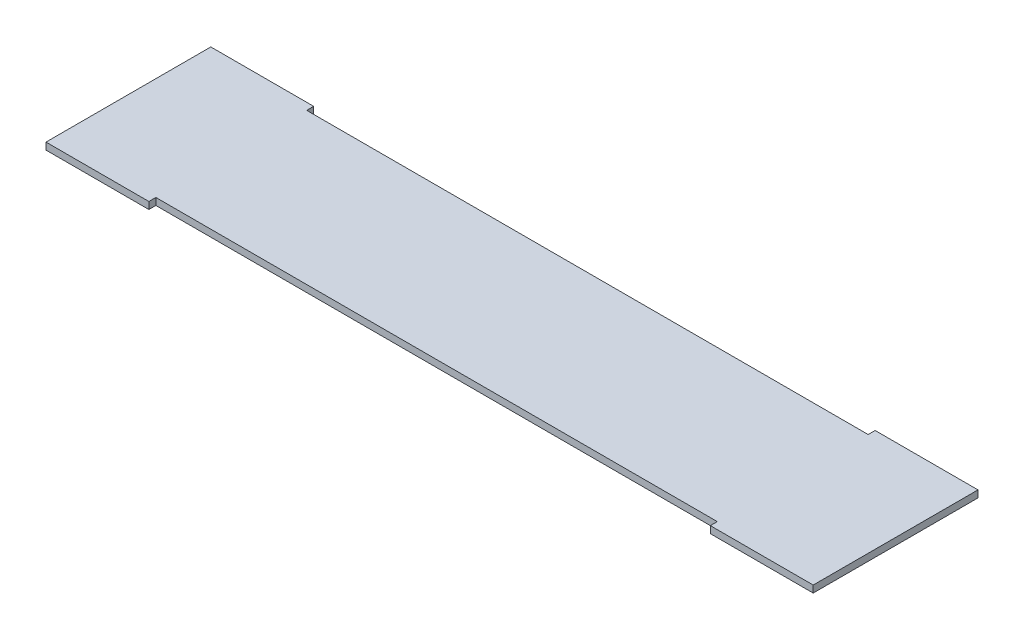
SolidWorks part; units mm, degrees
ref_plane "Front Plane" through (0, 0, 0) normal (0, 0, 1) x (1, 0, 0)
ref_plane "Top Plane" through (0, 0, 0) normal (0, 1, 0) x (1, 0, 0)
ref_plane "Right Plane" through (0, 0, 0) normal (1, 0, 0) x (0, 0, -1)
other "Default"
sketch "Sketch1" plane through (0, 0, 0) normal (0, 1, 0) x (1, 0, 0)
  line L0 (-349.15, 75) -> (-349.15, -75)
  line L1 (-349.15, -75) -> (-255.5, -75)
  line L2 (-255.5, -75) -> (-255.5, -68.65)
  line L3 (-255.5, -68.65) -> (255.5, -68.65)
  line L4 (255.5, -68.65) -> (255.5, -75)
  line L5 (255.5, -75) -> (349.15, -75)
  line L6 (349.15, -75) -> (349.15, 75)
  line L7 (349.15, 75) -> (255.5, 75)
  line L8 (255.5, 75) -> (255.5, 68.65)
  line L9 (255.5, 68.65) -> (-255.5, 68.65)
  line L10 (-255.5, 68.65) -> (-255.5, 75)
  line L11 (-255.5, 75) -> (-349.15, 75)
  point P11 (0, -68.65)
  point P13 (349.15, 0)
  dimension "D1" = 150
  dimension "D2" = 6.35
  dimension "TabWidth" = 93.65
  dimension "Width" = 698.3
extrude "Boss-Extrude1" add sketch "Sketch1" along normal mid plane 6.35
